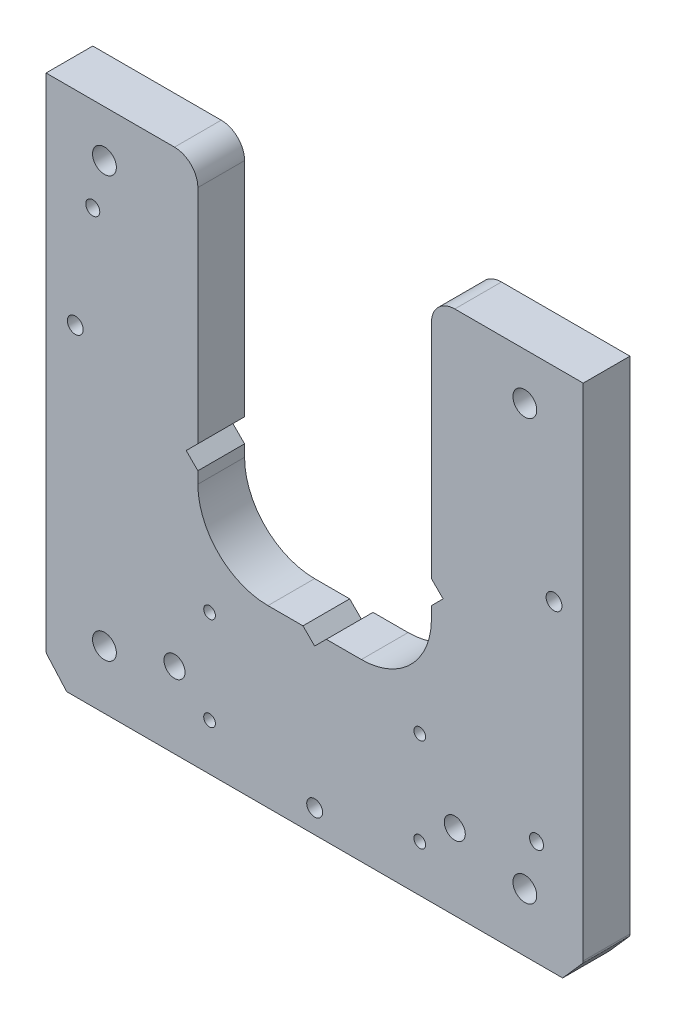
SolidWorks part; units mm, degrees
material "6061 Alloy"
ref_plane "Front Plane" through (0, 0, 0) normal (0, 0, 1) x (1, 0, 0)
ref_plane "Top Plane" through (0, 0, 0) normal (0, 1, 0) x (1, 0, 0)
ref_plane "Right Plane" through (0, 0, 0) normal (1, 0, 0) x (0, 0, -1)
imported_body "Imported3" [suppressed]
imported_body "Imported4" [suppressed]
imported_body "Imported5" [suppressed]
imported_body "Imported6" [suppressed]
ref_plane "Plane2" through (0, 0, 0) normal (0, 0, -1) x (-1, 0, 0)
sketch "Sketch18" plane through (0, 0, 0) normal (0, 0, -1) x (-1, 0, 0)
  line L0 (20, -40) -> (-20, -40)
  line L1 (-50, -10) -> (-50, -5)
  line L2 (-50, -5) -> (-55, 0)
  line L3 (-55, 0) -> (-50, 5)
  line L4 (-50, 5) -> (-50, 100)
  line L5 (-60, 110) -> (-165, 110)
  line L6 (-175, 100) -> (-175, 40)
  line L7 (-165, 30) -> (-155, 30)
  line L8 (-115, -10) -> (-115, -104.2438)
  line L9 (-114.4997, -105.567) -> (-40.5971, -189.3232)
  line L10 (-39.0975, -190) -> (39.0975, -190)
  line L11 (40.5971, -189.3232) -> (114.4997, -105.567)
  line L12 (115, -104.2438) -> (115, -10)
  line L13 (155, 30) -> (165, 30)
  line L14 (175, 40) -> (175, 100)
  line L15 (165, 110) -> (60, 110)
  line L16 (50, 100) -> (50, 5)
  line L17 (50, 5) -> (55, 0)
  line L18 (55, 0) -> (50, -5)
  line L19 (50, -5) -> (50, -10)
  arc A0 (-20, -40) -> (-50, -10) centre (-20, -10) cw
  arc A1 (-50, 100) -> (-60, 110) centre (-60, 100) ccw
  arc A2 (-165, 110) -> (-175, 100) centre (-165, 100) ccw
  arc A3 (-175, 40) -> (-165, 30) centre (-165, 40) ccw
  arc A4 (-155, 30) -> (-115, -10) centre (-155, -10) cw
  arc A5 (-115, -104.2438) -> (-114.4997, -105.567) centre (-113, -104.2438) ccw
  arc A6 (-40.5971, -189.3232) -> (-39.0975, -190) centre (-39.0975, -188) ccw
  arc A7 (39.0975, -190) -> (40.5971, -189.3232) centre (39.0975, -188) ccw
  arc A8 (114.4997, -105.567) -> (115, -104.2438) centre (113, -104.2438) ccw
  arc A9 (115, -10) -> (155, 30) centre (155, -10) cw
  arc A10 (165, 30) -> (175, 40) centre (165, 40) ccw
  arc A11 (175, 100) -> (165, 110) centre (165, 100) ccw
  arc A12 (60, 110) -> (50, 100) centre (60, 100) ccw
  arc A13 (50, -10) -> (20, -40) centre (20, -10) cw
extrude "Boss-Extrude2" add sketch "Sketch18" against normal blind 20 separate body
sketch "Sketch19" plane through (0, 0, 0) normal (0, 0, -1) x (-1, 0, 0)
  line L0 (-5, -40) -> (0, -45)
  line L1 (0, -45) -> (5, -40)
  line L2 (5, -40) -> (-5, -40)
extrude "Cut-Extrude2" cut sketch "Sketch19" against normal through all
hole_wizard "Ø5.0 (5) Diameter Hole2" positions "Sketch21" profile "Sketch20" hole size "Ø5.0" standard "ANSI Metric"
sketch "Sketch21" plane through (0, 0, 20) normal (0, 0, 1) x (1, 0, 0)
  point P0 (45, -55)
  point P1 (-45, -55)
  point P2 (-45, -95)
  point P3 (45, -95)
sketch "Sketch20" plane through (45, -55, 20) normal (1, 0, 0) x (0, -1, 0)
  line L0 (0, 0) -> (0, 16.5022)
  line L1 (0, 16.5022) -> (2.5, 15)
  line L2 (2.5, 15) -> (2.5, 0)
  line L5 (2.5, 0) -> (0, 0)
  line L10 (0, 16.5022) -> (-2.5, 15) construction
  line L11 (0, -6.35) -> (0, 107.95) construction
  dimension "Hole Dia." = 5
  dimension "Hole Depth" = 15
  dimension "Drill Angle" = 118
hole_wizard "Ø6.0 (6) Diameter Hole2" positions "Sketch23" profile "Sketch22" hole size "Ø6.0" standard "ANSI Metric"
sketch "Sketch23" plane through (0, 0, 0) normal (0, 0, -1) x (-1, 0, 0)
  point P0 (95, 70)
  point P1 (-95, -70)
sketch "Sketch22" plane through (-95, 70, 0) normal (1, 0, 0) x (0, 1, 0)
  line L0 (0, 0) -> (0, 20)
  line L1 (0, 20) -> (3, 20)
  line L2 (3, 20) -> (3, 0)
  line L5 (3, 0) -> (0, 0)
  line L11 (0, -6.35) -> (0, 107.95) construction
  dimension "Thru Hole Dia." = 6
  dimension "Thru Hole Depth" = 20
hole_wizard "Ø10.2 (10.2) Diameter Hole2" positions "Sketch25" profile "Sketch24" hole size "Ø10.2" standard "ANSI Metric"
sketch "Sketch25" plane through (0, 0, 0) normal (0, 0, -1) x (-1, 0, 0)
  point P0 (-90, -90)
  point P1 (90, -90)
  point P2 (-90, 90)
  point P3 (90, 90)
sketch "Sketch24" plane through (90, -90, 0) normal (1, 0, 0) x (0, 1, 0)
  line L0 (0, 0) -> (0, 20)
  line L1 (0, 20) -> (5.1, 20)
  line L2 (5.1, 20) -> (5.1, 0)
  line L5 (5.1, 0) -> (0, 0)
  line L11 (0, -6.35) -> (0, 107.95) construction
  dimension "Thru Hole Dia." = 10.2
  dimension "Thru Hole Depth" = 20
hole_wizard "Ø15.0 (15) Diameter Hole2" positions "Sketch27" profile "Sketch26" hole size "Ø15.0" standard "ANSI Metric"
sketch "Sketch27" plane through (0, 0, 0) normal (0, 0, -1) x (-1, 0, 0)
  point P0 (0, -150)
  point P1 (-135, 60)
  point P2 (135, 60)
sketch "Sketch26" plane through (0, -150, 0) normal (1, 0, 0) x (0, 1, 0)
  line L0 (0, 0) -> (0, 20)
  line L1 (0, 20) -> (7.5, 20)
  line L2 (7.5, 20) -> (7.5, 0)
  line L5 (7.5, 0) -> (0, 0)
  line L11 (0, -6.35) -> (0, 107.95) construction
  dimension "Thru Hole Dia." = 15
  dimension "Thru Hole Depth" = 20
hole_wizard "Ø6.8 (6.8) Diameter Hole2" positions "Sketch29" profile "Sketch28" hole size "Ø6.8" standard "ANSI Metric"
sketch "Sketch29" plane through (0, 0, 0) normal (0, 0, -1) x (-1, 0, 0)
  point P0 (102.5, 22.75)
  point P1 (0, -105)
  point P2 (-102.5, 22.75)
sketch "Sketch28" plane through (-102.5, 22.75, 0) normal (1, 0, 0) x (0, 1, 0)
  line L0 (0, 0) -> (0, 20)
  line L1 (0, 20) -> (3.4, 20)
  line L2 (3.4, 20) -> (3.4, 0)
  line L5 (3.4, 0) -> (0, 0)
  line L11 (0, -6.35) -> (0, 107.95) construction
  dimension "Thru Hole Dia." = 6.8
  dimension "Thru Hole Depth" = 20
hole_wizard "Ø9.0 (9) Diameter Hole2" positions "Sketch31" profile "Sketch30" hole size "Ø9.0" standard "ANSI Metric"
sketch "Sketch31" plane through (0, 0, 0) normal (0, 0, -1) x (-1, 0, 0)
  point P0 (60, -82.5)
  point P1 (-60, -82.5)
  point P2 (120, 95)
  point P3 (-120, 95)
sketch "Sketch30" plane through (-60, -82.5, 0) normal (1, 0, 0) x (0, 1, 0)
  line L0 (0, 0) -> (0, 20)
  line L1 (0, 20) -> (4.5, 20)
  line L2 (4.5, 20) -> (4.5, 0)
  line L5 (4.5, 0) -> (0, 0)
  line L11 (0, -6.35) -> (0, 107.95) construction
  dimension "Thru Hole Dia." = 9
  dimension "Thru Hole Depth" = 20
sketch "Sketch32" plane through (0, 0, 0) normal (0, 0, 1) x (1, 0, 0)
  line L1 (-115, -115) -> (115, -115)
  line L2 (-115, -115) -> (-115, 115)
  line L3 (-115, 115) -> (115, 115)
  line L4 (115, -115) -> (115, 115)
  line L5 (0, 115) -> (0, -115) construction
  line L6 (-115, 0) -> (115, 0) construction
  circle A0 centre (0, 0) radius 300
  point P0 (0, 0)
  dimension "D3" = 600
  dimension "D1" = 230
  dimension "D2" = 230
extrude "Cut-Extrude3" cut sketch "Sketch32" along normal through all contours A0 L4 L1 L2 L3 region at (-291.5147, 0, 0)
